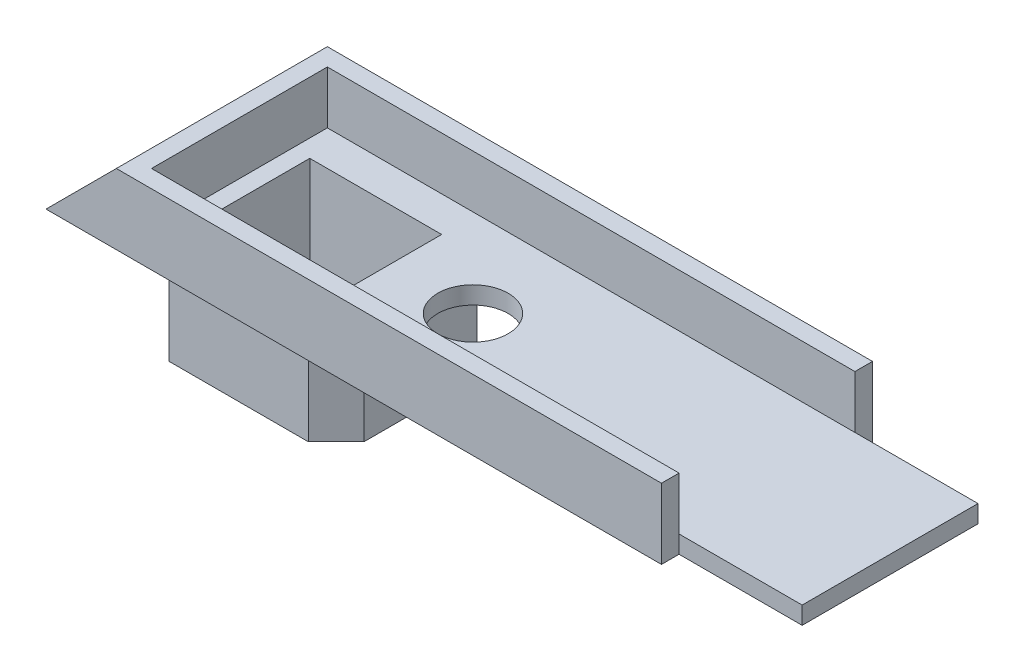
SolidWorks part; units mm, degrees
ref_plane "前视基准面" through (0, 0, 0) normal (0, 0, 1) x (1, 0, 0)
ref_plane "上视基准面" through (0, 0, 0) normal (0, 1, 0) x (1, 0, 0)
ref_plane "右视基准面" through (0, 0, 0) normal (1, 0, 0) x (0, 0, -1)
sketch "草图1" plane through (0, 0, 0) normal (0, 1, 0) x (1, 0, 0)
  line L0 (-12.5242, -6.4845) -> (-12.5242, -12.4845)
  line L1 (-13.5242, -4.4845) -> (-4.0242, -4.4845) construction
  line L2 (-13.5242, -4.4845) -> (-13.5242, -14.4845) construction
  line L3 (-13.5242, -14.4845) -> (-4.0242, -14.4845) construction
  line L4 (23.4758, -4.4845) -> (23.4758, -14.4845)
  line L5 (-12.5242, -12.4845) -> (-6.0242, -12.4845)
  line L6 (-5.0242, -11.4845) -> (-5.0242, -6.4845)
  line L7 (-5.0242, -6.4845) -> (-12.5242, -6.4845)
  line L8 (-6.0242, -12.4845) -> (-5.0242, -11.4845)
  line L9 (-53.0418, -9.4845) -> (30.158, -9.4845) construction
  line L13 (3.9758, -4.4845) -> (23.4758, -4.4845) construction
  line L17 (3.9758, -14.4845) -> (23.4758, -14.4845) construction
  line L18 (-4.0242, -3.4845) -> (-14.5242, -3.4845)
  line L19 (-14.5242, -3.4845) -> (-14.5242, -15.4845)
  line L20 (-14.5242, -15.4845) -> (-4.0242, -15.4845)
  line L21 (2.9758, -3.4845) -> (16.4758, -3.4845)
  line L22 (16.4758, -3.4845) -> (16.4758, -4.4845)
  line L23 (16.4758, -15.4845) -> (16.4758, -14.4845)
  line L24 (2.9758, -15.4845) -> (16.4758, -15.4845)
  line L25 (16.4758, -4.4845) -> (23.4758, -4.4845)
  line L26 (23.4758, -14.4845) -> (16.4758, -14.4845)
  line L27 (-4.0242, -15.4845) -> (2.9758, -15.4845)
  line L28 (-4.0242, -3.4845) -> (2.9758, -3.4845)
  point P12 (23.4758, -9.4845)
  dimension "D1" = 37
  dimension "D2" = 10
  dimension "D3" = 6
  dimension "D4" = 2
  dimension "D5" = 7.5
  dimension "D6" = 135
  dimension "D7" = 1
  dimension "D8" = 5
  dimension "D10" = 1
  dimension "D11" = 1
  dimension "D12" = 1
  dimension "D14" = 12.5
extrude "凸台-拉伸1" add sketch "草图1" along normal blind 1
sketch "草图2" plane through (0, 0, 0) normal (0, -1, 0) x (1, 0, 0)
  line L0 (-12.5242, 12.4845) -> (-6.0242, 12.4845)
  line L1 (-12.5242, 12.4845) -> (-6.0242, 12.4845) construction
  line L2 (-6.0242, 12.4845) -> (-5.0242, 11.4845) construction
  line L3 (-6.0242, 12.4845) -> (-5.0242, 11.4845)
  line L4 (-5.0242, 11.4845) -> (-5.0242, 6.4845)
  line L5 (-5.0242, 6.4845) -> (-12.5242, 6.4845)
  line L6 (-12.5242, 6.4845) -> (-12.5242, 12.4845)
  line L7 (-13.5242, 5.4845) -> (-13.5242, 13.4845)
  line L8 (-13.5242, 13.4845) -> (-5.61, 13.4845)
  line L9 (-5.61, 13.4845) -> (-4.0242, 11.8987)
  line L10 (-4.0242, 11.8987) -> (-4.0242, 5.4845)
  line L11 (-4.0242, 5.4845) -> (-13.5242, 5.4845)
  dimension "D1" = 1
extrude "凸台-拉伸2" add sketch "草图2" along normal blind 6
sketch "草图3" plane through (0, 1, 0) normal (0, 1, 0) x (1, 0, 0)
  line L1 (-18.2722, -9.4845) -> (28.1646, -9.4845) construction
  line L2 (-14.5242, -3.4845) -> (-14.5242, -15.4845) construction
  circle A0 centre (-0.2442, -9.4845) radius 2
  dimension "D1" = 4
  dimension "D2" = 14.28
extrude "切除-拉伸1" cut sketch "草图3" against normal blind 1
sketch "草图4" plane through (0, 1, 0) normal (0, 1, 0) x (1, 0, 0)
  line L0 (-14.5242, -3.4845) -> (16.4758, -3.4845)
  line L1 (16.4758, -3.4845) -> (16.4758, -4.4845)
  line L2 (16.4758, -4.4845) -> (-13.5242, -4.4845)
  line L3 (-14.5242, -3.4845) -> (-14.5242, -15.4845)
  line L4 (-14.5242, -15.4845) -> (16.4758, -15.4845)
  line L5 (16.4758, -15.4845) -> (16.4758, -14.4845)
  line L6 (16.4758, -14.4845) -> (-13.5242, -14.4845)
  line L7 (-13.5242, -14.4845) -> (-13.5242, -4.4845)
  dimension "D1" = 1
extrude "凸台-拉伸3" add sketch "草图4" along normal blind 3
sketch "草图5" plane through (0, 4, 0) normal (0, 1, 0) x (1, 0, 0)
  line L0 (-14.5242, -3.4845) -> (-14.5242, -15.4845)
  line L1 (-14.5242, -15.4845) -> (-4.0242, -15.4845)
  line L2 (-14.5242, -15.4845) -> (16.4758, -15.4845) construction
  line L3 (-14.5242, -3.4845) -> (-4.0242, -3.4845)
  line L4 (16.4758, -3.4845) -> (-14.5242, -3.4845) construction
  line L5 (-4.0242, -3.4845) -> (-4.0242, -10.3045)
  line L6 (-6.7242, -10.3045) -> (-6.7242, -12.8045)
  line L7 (-6.7242, -12.8045) -> (-4.0242, -12.8045)
  line L9 (-4.0242, -10.3045) -> (-6.7242, -10.3045)
  line L10 (-4.0242, -12.8045) -> (-4.0242, -15.4845)
  dimension "D1" = 7.8
  dimension "D2" = 2.68
  dimension "D3" = 2.5
  dimension "D4" = 2.7
sketch "草图6" plane through (0, 1, 0) normal (0, 1, 0) x (1, 0, 0)
  line L0 (-14.5242, -3.4845) -> (-14.5242, -15.4845) construction
  line L2 (-17.6881, -9.4845) -> (25.119, -9.4845) construction
  point P0 (-14.5242, -9.4845)
sketch "草图7" plane through (0, 0, 15.4845) normal (0, 0, 1) x (1, 0, 0)
  line L0 (-14.5242, 0) -> (-14.5242, 4)
  line L1 (-14.5242, 4) -> (-18.5242, 0)
  line L3 (-18.5242, 0) -> (-14.5242, 0)
  point P4 (0, 0)
  point P8 (0, 0)
  dimension "D1" = 45
extrude "凸台-拉伸4" add sketch "草图7" against normal blind 12
